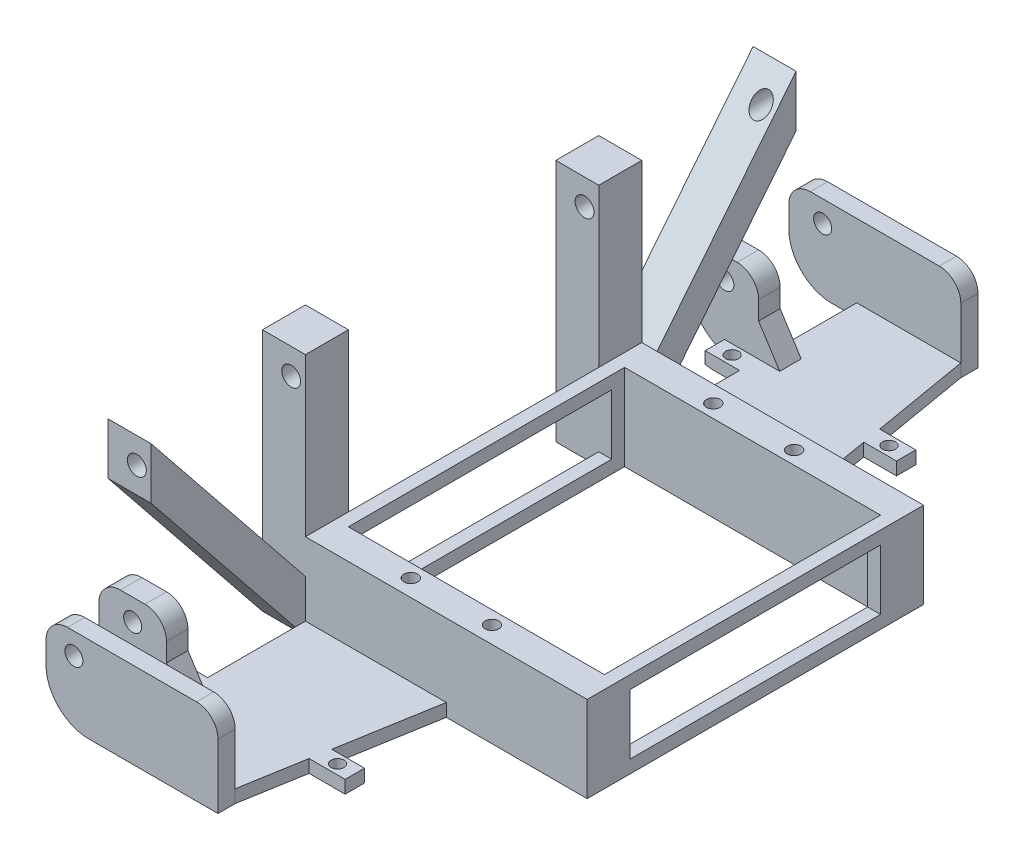
SolidWorks part; units mm, degrees
note: The reader was unsure of these and kept them because the rebuilt part matched: shared geometry of "Sketch1<8>".
ref_plane "Front Plane" through (0, 0, 0) normal (0, 0, 1) x (1, 0, 0)
ref_plane "Top Plane" through (0, 0, 0) normal (0, 1, 0) x (1, 0, 0)
ref_plane "Right Plane" through (0, 0, 0) normal (1, 0, 0) x (0, 0, -1)
sketch "Sketch1" plane through (0, 0, 0) normal (0, 1, 0) x (1, 0, 0)
  line L0 (0, 39.1145) -> (0, -39.1145)
  line L1 (0, -39.1145) -> (65.532, -39.1145)
  line L2 (65.532, -39.1145) -> (65.532, 39.1145)
  line L3 (65.532, 39.1145) -> (0, 39.1145)
  line L4 (0, 39.1145) -> (0, 89.1145)
  line L5 (0, 89.1145) -> (24.2, 89.1145)
  line L6 (24.2, 89.1145) -> (32.766, 39.1145)
  line L7 (0, 39.1145) -> (32.766, 39.1145)
  line L8 (0, -39.1145) -> (0, -89.1145)
  line L9 (-8, 66.3645) -> (8, 66.3645)
  line L10 (-8, 66.3645) -> (-8, 61.8645)
  line L11 (-8, 61.8645) -> (8, 61.8645)
  line L12 (8, 66.3645) -> (8, 61.8645)
  line L13 (-55, 0) -> (55, 0) construction
  line L14 (3, 32.1145) -> (62.532, 32.1145)
  line L15 (20.483, 66.3645) -> (36.483, 66.3645)
  line L16 (20.483, 66.3645) -> (20.483, 61.8645)
  line L17 (20.483, 61.8645) -> (36.483, 61.8645)
  line L18 (36.483, 66.3645) -> (36.483, 61.8645)
  line L19 (3, 32.1145) -> (3, -32.1145)
  line L20 (3, -32.1145) -> (62.532, -32.1145)
  line L21 (0, -55) -> (0, 55) construction
  line L22 (0, -89.1145) -> (24.2, -89.1145)
  line L23 (24.2, -89.1145) -> (32.766, -39.1145)
  line L24 (32.766, -39.1145) -> (0, -39.1145)
  line L25 (62.532, 32.1145) -> (62.532, -32.1145)
  line L26 (20.483, -61.8645) -> (36.483, -61.8645)
  line L27 (20.483, -61.8645) -> (20.483, -66.3645)
  line L28 (20.483, -66.3645) -> (36.483, -66.3645)
  line L29 (36.483, -61.8645) -> (36.483, -66.3645)
  line L30 (3, 32.1145) -> (62.532, -32.1145) construction
  line L31 (3, -32.1145) -> (62.532, 32.1145) construction
  line L32 (-8, -61.8645) -> (8, -61.8645)
  line L33 (-8, -61.8645) -> (-8, -66.3645)
  line L34 (-8, -66.3645) -> (8, -66.3645)
  line L35 (8, -61.8645) -> (8, -66.3645)
  line L36 (0, 89.1145) -> (0, 91.1145)
  line L37 (0, 91.1145) -> (24.2, 91.1145)
  line L38 (24.2, 91.1145) -> (24.2, 89.1145)
  line L39 (0, -89.1145) -> (0, -81.0311)
  line L40 (0, -81.0311) -> (37.5753, -81.0311)
  line L41 (37.5753, -81.0311) -> (37.5753, -89.1145)
  line L42 (37.5753, -89.1145) -> (0, -89.1145)
  line L43 (32.766, 39.1145) -> (0, 39.1145)
  line L44 (32.766, -39.1145) -> (0, -39.1145)
  circle A0 centre (20.574, 35.1758) radius 1.6
  circle A1 centre (39.37, 35.1758) radius 1.5999
  circle A2 centre (20.574, -35.1795) radius 1.6
  circle A3 centre (39.4509, -35.1795) radius 1.5999
  circle A4 centre (-4, 64.1145) radius 1.5
  circle A5 centre (32.483, 64.1145) radius 1.5
  circle A6 centre (-4, -64.1145) radius 1.5
  circle A8 centre (32.483, -64.1145) radius 1.5
  point P8 (0, 64.1145)
  point P21 (28.483, 64.1145)
  point P30 (28.483, -64.1145)
  point P40 (0, -64.1145)
  point P47 (32.766, 0)
  dimension "D12" = 3
  dimension "D14" = 3
  dimension "D23" = 3
  dimension "D24" = 4
  dimension "D26" = 3
  dimension "D27" = 7
  dimension "D1" = 65.532
  dimension "D2" = 78.229
  dimension "D3" = 50
  dimension "D4" = 24.2
  dimension "D5" = 7
  dimension "D6" = 50
  dimension "D7" = 16
  dimension "D8" = 16
  dimension "D9" = 4.5
  dimension "D10" = 4.5
  dimension "D11" = 8
  dimension "D13" = 4
  dimension "D15" = 4
  dimension "D16" = 44.483
  dimension "D17" = 50
  dimension "D18" = 70.3553
  dimension "D19" = 16
  dimension "D20" = 16
  dimension "D21" = 4.5
  dimension "D22" = 4.5
  dimension "D25" = 4
  dimension "D28" = 3
  dimension "D29" = 3
  dimension "D30" = 2.25
  dimension "D31" = 2.25
  dimension "D32" = 2.25
  dimension "D33" = 2.25
  dimension "D34" = 36.483
  dimension "D35" = 36.483
  dimension "D36" = 2
  dimension "D37" = 3.935
extrude "Boss-Extrude1" add sketch "Sketch1" along normal blind 3 contours L10 L11 L4 L9 A4 | L12 L9 L4 L11 | L17 L16 L15 L6 L5 L4 L9 L12 L11 L3 | L16 L17 L6 L15 | L18 L15 L6 L17 A5 | L2 L3 L0 L1 A3 A2 A1 A0 L14 L25 L20 L19 | L32 L35 L34 L8 L22 L23 L28 L27 L26 L1 | L27 L28 L23 L26 | L29 L26 L23 L28 A8 | L35 L32 L8 L34 | L33 L34 L8 L32 A6
sketch "Sketch2" plane through (0, 0, 0) normal (0, 1, 0) x (1, 0, 0)
  line L11 (25.5849, -81.0373) -> (25.5849, -85.0373)
  line L12 (25.5849, -85.0373) -> (-14.4151, -85.0373)
  line L13 (-14.4151, -85.0373) -> (-14.4151, -81.0373)
  line L14 (-14.4151, -81.0373) -> (25.5849, -81.0373)
  line L15 (24.2, 89.1145) -> (24.2, 93.1145)
  line L16 (24.2, 93.1145) -> (-15.8, 93.1145)
  line L17 (-15.8, 93.1145) -> (-15.8, 89.1145)
  line L18 (-15.8, 89.1145) -> (24.2, 89.1145)
  dimension "D1" = 40
  dimension "D2" = 4
  dimension "D3" = 40
  dimension "D4" = 4
extrude "Boss-Extrude2" add sketch "Sketch2" along normal blind 20
sketch "Sketch3" plane through (0, 0, 0) normal (0, 0, 1) x (1, 0, 0)
  line L2 (0, -16.5) -> (0, 16.5) construction
  circle A4 centre (0, 14.8653) radius 2
  dimension "D4" = 4
fillet "Fillet2" radius 5 2 edges at (25.5849, 20, 83.0373) (-14.4151, 20, 83.0373)
fillet "Fillet3" radius 10 1 edges at (-14.4151, 0, 83.0373)
extrude "Boss-Extrude3" add sketch "Sketch1<8>" along normal blind 20 contours L2 L3 L0 L1 A3 A2 A1 A0 L14 L25 L20 L19
sketch "Sketch1<8>" plane through (0, 0, 0) normal (0, 1, 0) x (1, 0, 0) same geometry as "Sketch1"
sketch "Sketch5" plane through (0, 0, 0) normal (0, 1, 0) x (1, 0, 0)
  circle A0 centre (20.574, -35.1795) radius 2.5
  circle A1 centre (39.4509, -35.1795) radius 2.5
  circle A2 centre (20.574, 35.1758) radius 2.5
  circle A3 centre (39.37, 35.1758) radius 2.5
  dimension "D1" = 5
extrude "Cut-Extrude2" cut sketch "Sketch5" along normal blind 5
sketch "Sketch7" plane through (0, 0, 0) normal (1, 0, 0) x (0, 0, -1)
  line L0 (-29.1145, 17) -> (-29.1145, 3)
  line L1 (-29.1145, 3) -> (29.1145, 3)
  line L2 (29.1145, 3) -> (29.1145, 17)
  line L3 (29.1145, 17) -> (-29.1145, 17)
  line L4 (-39.1145, 20) -> (-39.1145, 0) construction
  line L5 (39.1145, 20) -> (39.1145, 0) construction
  line L6 (-39.1145, 20) -> (39.1145, 20) construction
  line L7 (55, 0) -> (-55, 0) construction
  dimension "D1" = 10
  dimension "D2" = 10
  dimension "D3" = 3
  dimension "D4" = 3
extrude "Cut-Extrude3" cut sketch "Sketch7" along normal through all
sketch "Sketch8" plane through (0, 0, -93.1145) normal (0, 0, -1) x (-1, 0, 0)
  line L1 (15.8, 0) -> (-24.2, 0) construction
  circle A0 centre (7.9316, 15) radius 2.1
  dimension "D1" = 4.2
  dimension "D2" = 15
extrude "Cut-Extrude4" cut sketch "Sketch8" against normal blind 211
fillet "Fillet4" radius 10 1 edges at (-15.8, 0, -91.1145)
fillet "Fillet5" radius 5 2 edges at (24.2, 20, -91.1145) (-15.8, 20, -91.1145)
sketch "Sketch9" plane through (0, 0, 0) normal (-1, 0, 0) x (0, 0, 1)
  line L1 (-39.1145, 0) -> (-29.1145, 0)
  line L2 (-39.1145, 0) -> (-39.1145, 56.69)
  line L3 (-39.1145, 56.69) -> (-29.1145, 56.69)
  line L4 (-29.1145, 0) -> (-29.1145, 56.69)
  line L5 (61.8645, 0) -> (-61.8645, 0) construction
  line L6 (-29.1145, 3) -> (-29.1145, 17) construction
  dimension "D1" = 56.69
extrude "Boss-Extrude4" add sketch "Sketch9" along normal blind 10
sketch "Sketch12" plane through (0, 0, -75.0106) normal (0, 0, 1) x (1, 0, 0)
  line L1 (-10.0286, 44.6914) -> (3.4054, 44.6914)
  line L2 (-10.0286, 44.6914) -> (-10.0286, 56.6914)
  line L3 (-10.0286, 56.6914) -> (3.4054, 56.6914)
  line L4 (3.4054, 44.6914) -> (3.4054, 56.6914)
  line L5 (-10.0286, 44.6914) -> (3.4054, 56.6914) construction
  line L6 (-10.0286, 56.6914) -> (3.4054, 44.6914) construction
  point P0 (-3.3116, 50.6914)
  dimension "D1" = 12
sketch "Sketch11" plane through (-10, 0, 0) normal (-1, 0, 0) x (0, 0, 1)
  line L0 (-39.1145, 0) -> (-75.0106, 44.6914)
  line L1 (-75.0106, 44.6914) -> (-75.0106, 56.6914)
  line L2 (-39.1145, 0) -> (-39.1145, 12)
  line L4 (-29.1145, 56.69) -> (-75.0106, 59.849) construction
  line L5 (-75.0106, 56.6914) -> (-75.0106, 44.6914) construction
  line L6 (-75.0106, 44.6914) -> (-75.0106, 56.6914) construction
  line L7 (-75.0106, 44.6914) -> (-75.0106, 56.6914) construction
  line L8 (-39.1145, 56.69) -> (-39.1145, 0) construction
  line L9 (-75.0106, 56.6914) -> (-39.1145, 12)
  dimension "D1" = 12
extrude "Boss-Extrude5" add sketch "Sketch11" against normal blind 10
sketch "Sketch15" plane through (0, 0, -66.3645) normal (0, 0, -1) x (-1, 0, 0)
  line L0 (15.8, 0) -> (-24.2, 0) construction
  line L1 (15.8, 0) -> (0, 0)
  line L2 (15.8, 0) -> (15.8, 20)
  line L3 (15.8, 20) -> (0.0744, 20)
  line L5 (-24.2, 0) -> (15.8, 0) construction
  line L6 (-19.2, 20) -> (10.8, 20) construction
  line L7 (0, 3) -> (-4.8386, 3)
  line L9 (-4.8386, 3) -> (0.0744, 10.6808)
  line L10 (0.0744, 10.6808) -> (0.0744, 20)
  line L11 (0, 3) -> (0, 0)
  point P16 (0.0744, 10.7974)
extrude "Boss-Extrude6" add sketch "Sketch15" along normal blind 5
fillet "Fillet6" radius 5 2 edges at (-15.8, 20, -68.8645) (-0.0744, 20, -68.8645)
fillet "Fillet7" radius 10 1 edges at (-15.8, 0, -68.8645)
sketch "Sketch10" plane through (0, 0, -39.1145) normal (0, 0, -1) x (-1, 0, 0)
  circle A0 centre (3.3116, 50.6914) radius 2.2
  dimension "D1" = 4.4
extrude "Cut-Extrude5" cut sketch "Sketch10" against normal through all both and the other way through all
sketch "Sketch13" plane through (0, 0, 85.0373) normal (0, 0, 1) x (1, 0, 0)
  circle A0 centre (-7.9316, 15) radius 2.1
  dimension "D1" = 4.2
extrude "Cut-Extrude6" cut sketch "Sketch13" against normal through all
sketch "Sketch17" plane through (0, 0, -66.3645) normal (0, 0, 1) x (1, 0, 0)
  circle A0 centre (-7.9316, 15) radius 2.1
  dimension "D1" = 4.2
extrude "Cut-Extrude7" cut sketch "Sketch17" against normal through all
mirror "Mirror1" about plane through (0, 0, 0) normal (0, 0, 1) of "Cut-Extrude7", "Boss-Extrude6", "Boss-Extrude4", "Cut-Extrude5", "Boss-Extrude5", "Fillet6", "Fillet7"
